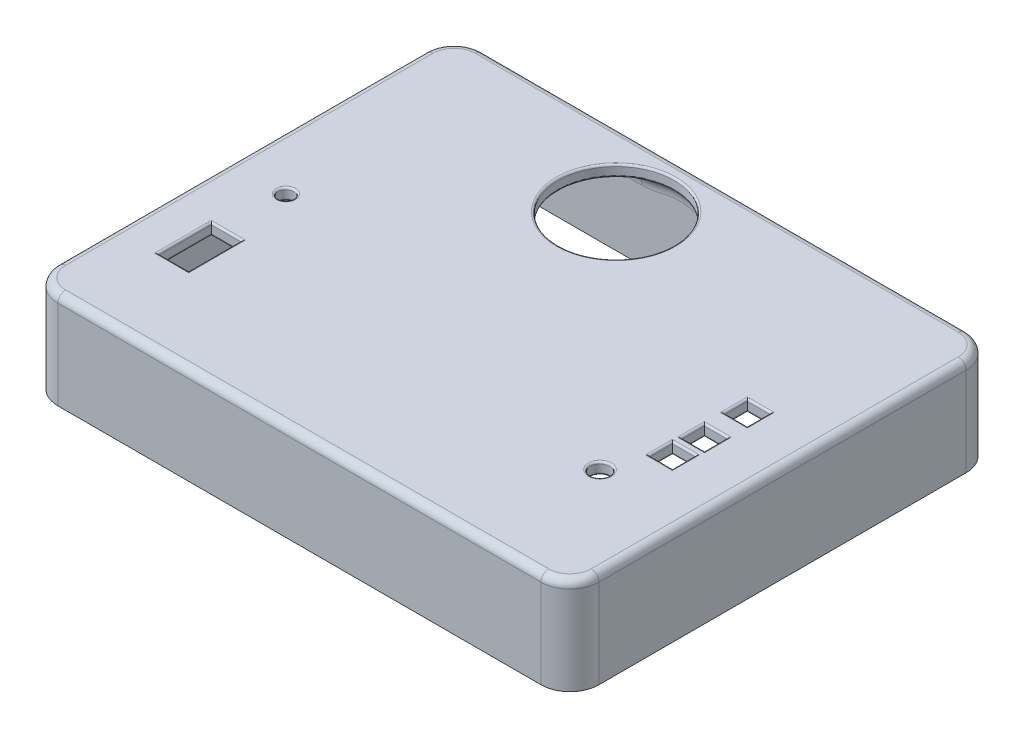
SolidWorks part; units mm, degrees
ref_plane "Front Plane" through (0, 0, 0) normal (0, 0, 1) x (1, 0, 0)
ref_plane "Top Plane" through (0, 0, 0) normal (0, 1, 0) x (1, 0, 0)
ref_plane "Right Plane" through (0, 0, 0) normal (1, 0, 0) x (0, 0, -1)
sketch "Sketch1" plane through (0, 0, 0) normal (0, 1, 0) x (1, 0, 0)
  line L1 (0, 0) -> (140, 0)
  line L2 (0, 0) -> (0, -110)
  line L3 (0, -110) -> (140, -110)
  line L4 (140, 0) -> (140, -110)
  dimension "D1" = 140
  dimension "D2" = 110
extrude "Boss-Extrude1" add sketch "Sketch1" along normal blind 25
sketch "Sketch2" plane through (0, 0, 0) normal (0, -1, 0) x (1, 0, 0)
  line L0 (0, 0) -> (0, 110) construction
  line L1 (3, 3) -> (137, 3)
  line L2 (3, 3) -> (3, 107)
  line L3 (3, 107) -> (137, 107)
  line L4 (137, 3) -> (137, 107)
  line L5 (140, 0) -> (0, 0) construction
  line L6 (0, 110) -> (140, 110) construction
  line L7 (140, 110) -> (140, 0) construction
  dimension "D1" = 3
  dimension "D2" = 3
  dimension "D3" = 3
  dimension "D4" = 3
extrude "Cut-Extrude1" cut sketch "Sketch2" against normal blind 22
sketch "Sketch3" plane through (0, 25, 0) normal (0, 1, 0) x (1, 0, 0)
  line L0 (0, -110) -> (140, -110) construction
  line L1 (11.26, -87.77) -> (19.12, -87.77)
  line L2 (11.26, -87.77) -> (11.26, -74.07)
  line L3 (11.26, -74.07) -> (19.12, -74.07)
  line L4 (19.12, -87.77) -> (19.12, -74.07)
  line L5 (0, 0) -> (0, -110) construction
  dimension "D1" = 7.86
  dimension "D2" = 13.7
  dimension "D3" = 22.23
  dimension "D4" = 11.26
extrude "Cut-Extrude2" cut sketch "Sketch3" against normal up to next
sketch "Sketch4" plane through (0, 25, 0) normal (0, 1, 0) x (1, 0, 0)
  line L0 (140, -110) -> (140, 0) construction
  line L1 (126.02, -69.48) -> (120.02, -69.48)
  line L2 (126.02, -69.48) -> (126.02, -63.48)
  line L3 (126.02, -63.48) -> (120.02, -63.48)
  line L4 (120.02, -69.48) -> (120.02, -63.48)
  line L5 (126.18, -61.37) -> (120.18, -61.37)
  line L6 (126.18, -61.37) -> (126.18, -55.37)
  line L7 (126.18, -55.37) -> (120.18, -55.37)
  line L8 (120.18, -61.37) -> (120.18, -55.37)
  line L9 (126.18, -50.28) -> (120.18, -50.28)
  line L10 (126.18, -50.28) -> (126.18, -44.28)
  line L11 (126.18, -44.28) -> (120.18, -44.28)
  line L12 (120.18, -50.28) -> (120.18, -44.28)
  line L13 (0, -110) -> (140, -110) construction
  line L14 (0, 0) -> (0, -110) construction
  line L15 (140, 0) -> (0, 0) construction
  circle A0 centre (14.5, -58) radius 2
  circle A1 centre (61.2, -19.24) radius 15
  circle A2 centre (116.92, -79.14) radius 2.5
  dimension "D14" = 5
  dimension "D17" = 4
  dimension "D19" = 30
  dimension "D1" = 6
  dimension "D2" = 6
  dimension "D3" = 6
  dimension "D4" = 6
  dimension "D5" = 6
  dimension "D6" = 6
  dimension "D7" = 2.11
  dimension "D8" = 5.09
  dimension "D9" = 23.08
  dimension "D10" = 0.16
  dimension "D11" = 40.52
  dimension "D12" = 13.98
  dimension "D13" = 30.86
  dimension "D15" = 14.5
  dimension "D16" = 52
  dimension "D18" = 19.24
  dimension "D20" = 61.2
extrude "Cut-Extrude3" cut sketch "Sketch4" against normal up to next
fillet "Fillet1" radius 2 4 edges at (70, 25, 0) (0, 25, 55) (70, 25, 110) (140, 25, 55)
fillet "Fillet2" radius 7.5 12 edges at (0.5858, 24.4142, 109.4142) (139.4142, 24.4142, 109.4142) (139.4142, 24.4142, 0.5858) (0.5858, 24.4142, 0.5858) (137, 11, 107) (137, 11, 3) (3, 11, 3) (3, 11, 107) (0, 11.5, 0) (140, 11.5, 0) (140, 11.5, 110) (0, 11.5, 110)
fillet "Fillet3" radius 0.5 38 edges at (123.02, 22, 69.48) (120.02, 22, 66.48) (123.02, 22, 63.48) (126.02, 22, 66.48) (126.18, 22, 58.37) (123.18, 22, 55.37) (123.18, 22, 61.37) (120.18, 22, 58.37) (120.18, 22, 47.28) (123.18, 22, 50.28) (123.18, 22, 44.28) (126.18, 22, 47.28) (14.5, 22, 60) (15.19, 22, 87.77) (15.19, 22, 74.07) (19.12, 22, 80.92) (11.26, 22, 80.92) (11.26, 25, 80.92) (15.19, 25, 87.77) (19.12, 25, 80.92) (15.19, 25, 74.07) (14.5, 25, 60) (126.18, 25, 47.28) (123.18, 25, 44.28) (120.18, 25, 47.28) (123.18, 25, 50.28) (120.18, 25, 58.37) (123.18, 25, 61.37) (126.18, 25, 58.37) (123.18, 25, 55.37) (120.02, 25, 66.48) (123.02, 25, 69.48) (126.02, 25, 66.48) (123.02, 25, 63.48) (116.92, 22, 81.64) (116.92, 25, 81.64) (61.2, 22, 34.24) (61.2, 25, 34.24)
fillet "Fillet4" radius 4 8 edges at (137, 22, 55) (134.8033, 22, 104.8033) (134.8033, 22, 5.1967) (70, 22, 3) (5.1967, 22, 5.1967) (3, 22, 55) (5.1967, 22, 104.8033) (70, 22, 107)
